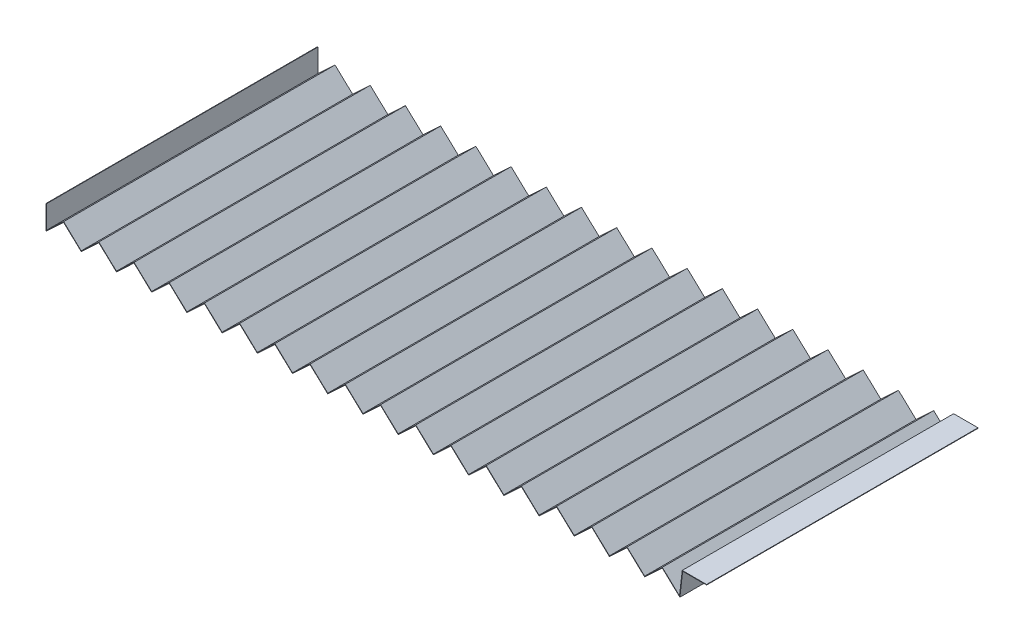
SolidWorks part; units mm, degrees
ref_plane "Front Plane" through (0, 0, 0) normal (0, 0, 1) x (1, 0, 0)
ref_plane "Top Plane" through (0, 0, 0) normal (0, 1, 0) x (1, 0, 0)
ref_plane "Right Plane" through (0, 0, 0) normal (1, 0, 0) x (0, 0, -1)
sketch "Sketch1" plane through (0, 0, 0) normal (0, 0, 1) x (1, 0, 0)
  line L0 (0, 0) -> (11.029, 10.3137)
  line L1 (11.029, 10.3137) -> (22.0579, 0)
  line L2 (0, 0) -> (511, 0) construction
  line L3 (22.0579, 0) -> (33.0869, 10.3137)
  line L4 (33.0869, 10.3137) -> (44.1159, 0)
  line L5 (44.1159, 0) -> (55.1449, 10.3137)
  line L6 (55.1449, 10.3137) -> (66.1738, 0)
  line L7 (66.1738, 0) -> (77.2028, 10.3137)
  line L8 (77.2028, 10.3137) -> (88.2318, 0)
  line L9 (88.2318, 0) -> (99.2608, 10.3137)
  line L10 (99.2608, 10.3137) -> (110.2897, 0)
  line L11 (110.2897, 0) -> (121.3187, 10.3137)
  line L12 (121.3187, 10.3137) -> (132.3477, 0)
  line L13 (132.3477, 0) -> (143.3767, 10.3137)
  line L14 (143.3767, 10.3137) -> (154.4056, 0)
  line L15 (154.4056, 0) -> (165.4346, 10.3137)
  line L16 (165.4346, 10.3137) -> (176.4636, 0)
  line L17 (176.4636, 0) -> (187.4926, 10.3137)
  line L18 (187.4926, 10.3137) -> (198.5215, 0)
  line L19 (0, 0) -> (0, 15.1)
  line L20 (198.5215, 0) -> (209.5505, 10.3137)
  line L21 (209.5505, 10.3137) -> (220.5795, 0)
  line L22 (220.5795, 0) -> (231.6085, 10.3137)
  line L23 (231.6085, 10.3137) -> (242.6374, 0)
  line L24 (242.6374, 0) -> (253.6664, 10.3137)
  line L25 (253.6664, 10.3137) -> (264.6954, 0)
  line L26 (264.6954, 0) -> (275.7244, 10.3137)
  line L27 (275.7244, 10.3137) -> (286.7533, 0)
  line L28 (286.7533, 0) -> (297.7823, 10.3137)
  line L29 (297.7823, 10.3137) -> (308.8113, 0)
  line L30 (308.8113, 0) -> (319.8403, 10.3137)
  line L31 (319.8403, 10.3137) -> (330.8692, 0)
  line L32 (330.8692, 0) -> (341.8982, 10.3137)
  line L33 (341.8982, 10.3137) -> (352.9272, 0)
  line L34 (352.9272, 0) -> (363.9562, 10.3137)
  line L35 (363.9562, 10.3137) -> (374.9851, 0)
  line L36 (374.9851, 0) -> (386.0141, 10.3137)
  line L37 (386.0141, 10.3137) -> (397.0431, 0)
  line L38 (397.0431, 0) -> (398.778, 15)
  line L39 (398.778, 15) -> (413.778, 15)
  line L41 (411.778, 34.6) -> (411.778, 13.6) construction
  dimension "D1" = 511
  dimension "D2" = 15.1
  dimension "D3" = 15
  dimension "D4" = 22.0579
  dimension "D6" = 15
  dimension "D7" = 2
  dimension "D5" = 18
extrude "Extrude-Thin1" add sketch "Sketch1" along normal mid plane 170 thin thin type one direction reverse wall 0.3
